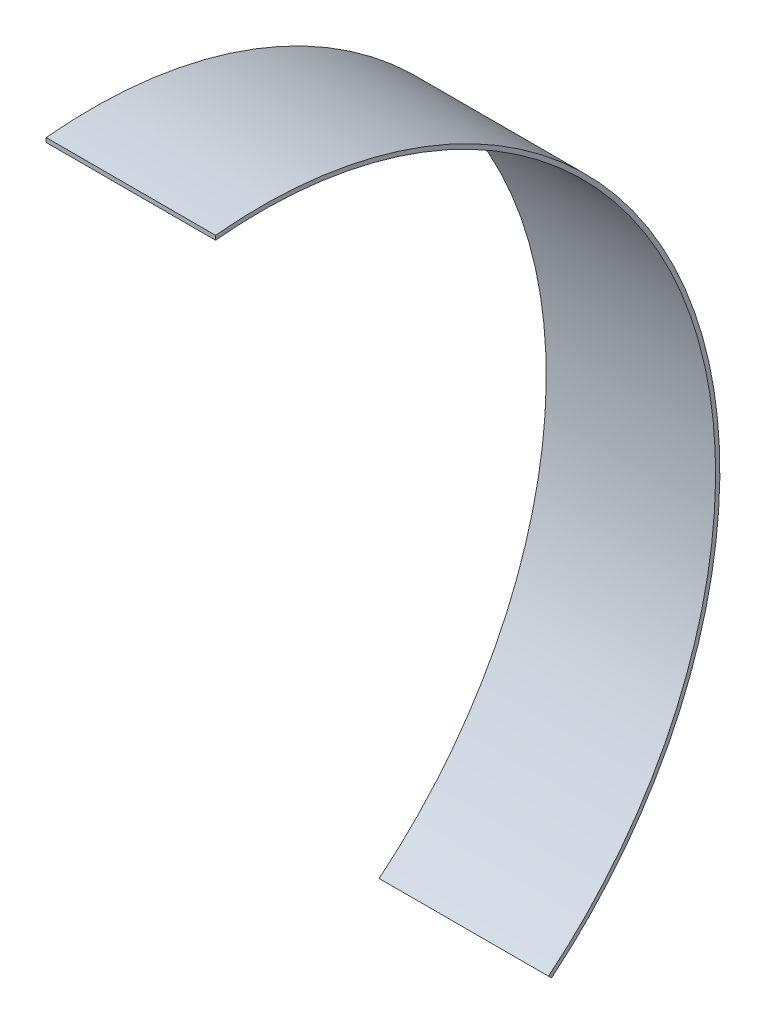
SolidWorks part; units mm, degrees
ref_plane "Front Plane" through (0, 0, 0) normal (0, 0, 1) x (1, 0, 0)
ref_plane "Top Plane" through (0, 0, 0) normal (0, 1, 0) x (1, 0, 0)
ref_plane "Right Plane" through (0, 0, 0) normal (1, 0, 0) x (0, 0, -1)
sketch "Sketch1" plane through (0, 0, 0) normal (1, 0, 0) x (0, 0, -1)
  line L4 (0, 0) -> (0, 75) construction
  line L5 (0, 0) -> (53.033, -53.033) construction
  line L6 (-7.5, -3.1066) -> (47.4639, -58.0705)
  line L7 (-7.5, -3.1066) -> (-7.5, 74.6241)
  line L8 (-7.5, -3.1066) -> (-7.5, 95.6451) construction
  line L9 (0, 0) -> (0, 95.6451) construction
  line L10 (-7.5, -3.1066) -> (59.8943, -70.5009) construction
  line L11 (0, 0) -> (65.1976, -65.1976) construction
  circle A0 centre (0, 0) radius 75
  circle A1 centre (0, 0) radius 74.3
  point P5 (25, -70.7107)
  dimension "D1" = 150
  dimension "D2" = 0.7
  dimension "D3" = 135
  dimension "D4" = 7.5
  dimension "D5" = 25
extrude "Boss-Extrude1" add sketch "Sketch1" along normal mid plane 27.7 contours A1 L6 A0 L7 region at (0, -31.9332, -67.2611)
